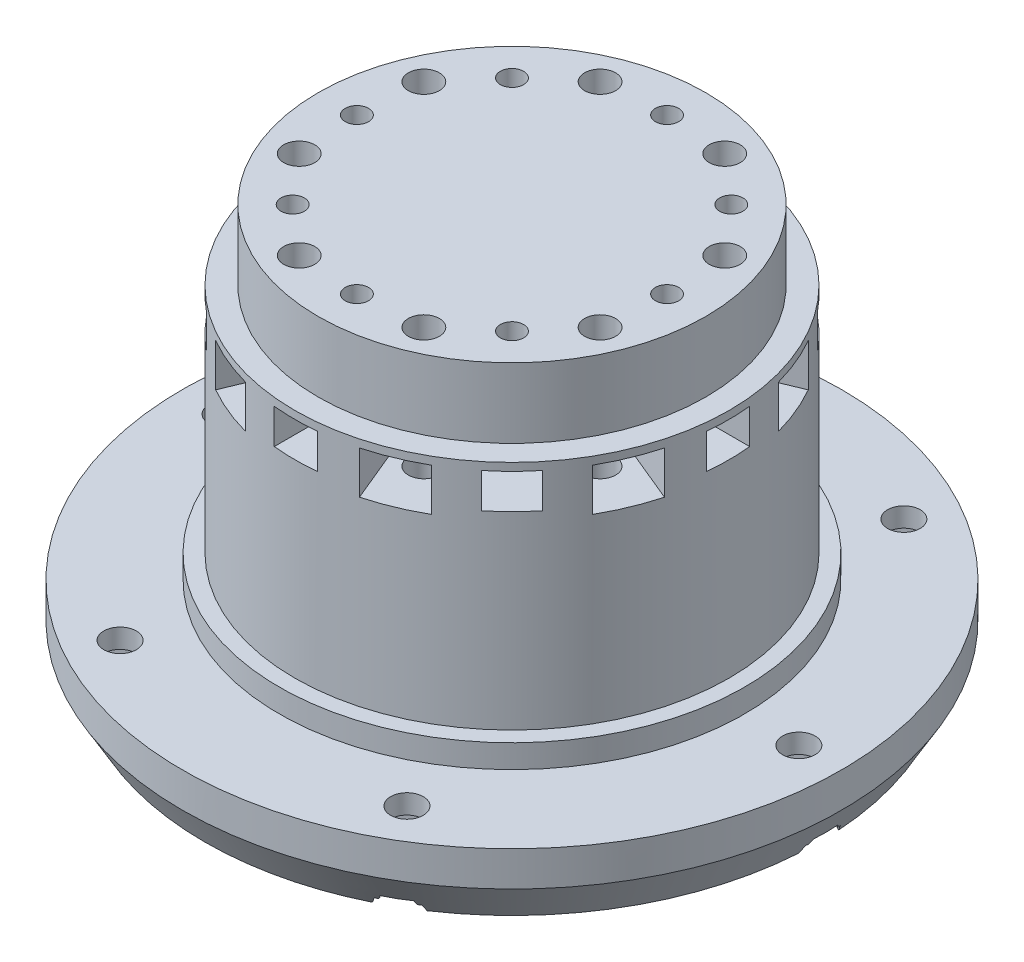
SolidWorks part; units mm, degrees
material "ABS"
ref_plane "Front Plane" through (0, 0, 0) normal (0, 0, 1) x (1, 0, 0)
ref_plane "Top Plane" through (0, 0, 0) normal (0, 1, 0) x (1, 0, 0)
ref_plane "Right Plane" through (0, 0, 0) normal (1, 0, 0) x (0, 0, -1)
sketch "Sketch1" plane through (0, 0, 0) normal (0, 0, 1) x (1, 0, 0)
  line L0 (0, 0) -> (0, 51.7742) construction
  line L1 (0, 0) -> (-42.5, 0)
  line L2 (-42.5, 0) -> (-42.5, 9.5)
  line L3 (-42.5, 9.5) -> (-30, 9.5)
  line L10 (0, 12.5) -> (0, 0)
  line L13 (-30, 9.5) -> (-30, 12.5)
  line L14 (-30, 12.5) -> (0, 12.5)
  dimension "D1" = 60
  dimension "D2" = 9.5
  dimension "D3" = 3
  dimension "D4" = 85
revolve "Revolve1" add sketch "Sketch1" angle 360 about L0
sketch "Sketch2" plane through (0, 0, 0) normal (0, 0, 1) x (1, 0, 0)
  line L0 (0, 0) -> (0, 30.5348) construction
  line L1 (-28, 41.4) -> (-28, 12.5)
  line L2 (0, -8.6) -> (-15, -8.6)
  line L3 (-15, -8.6) -> (-15, -0.6)
  line L4 (-15, -0.6) -> (-17.5, -0.6)
  line L5 (-17.5, -0.6) -> (-17.5, 0)
  line L6 (-42.5, 0) -> (42.5, 0) construction
  line L7 (-17.5, 0) -> (0, 0)
  line L8 (0, 0) -> (0, -8.6)
  line L9 (0, 51.4) -> (-25, 51.4)
  line L10 (-25, 51.4) -> (-25, 42.4)
  line L11 (-25, 42.4) -> (-28, 42.4)
  line L12 (-28, 42.4) -> (-28, 41.4)
  line L13 (30, 12.5) -> (-30, 12.5) construction
  line L14 (-28, 41.4) -> (0, 41.4) construction
  line L15 (0, 41.4) -> (0, 51.4)
  line L16 (-28, 12.5) -> (0, 12.5)
  line L17 (0, 12.5) -> (0, 41.4)
  dimension "D1" = 30
  dimension "D2" = 2.5
  dimension "D3" = 0.6
  dimension "D4" = 8
  dimension "D5" = 9
  dimension "D6" = 50
  dimension "D7" = 3
  dimension "D8" = 51
  dimension "D9" = 1
revolve "Revolve2" add sketch "Sketch2" angle 360 about L0
sketch "Sketch21" plane through (0, -8.6, 0) normal (0, -1, 0) x (1, 0, 0)
  circle A0 centre (0, 0) radius 3.175
  dimension "D1" = 6.35
extrude "Cut-Extrude13" cut sketch "Sketch21" against normal blind 3.16
sketch "Sketch24" [suppressed] plane through (0, -8.6, 0) normal (0, -1, 0) x (1, 0, 0)
  line L1 (-7.5, -0.75) -> (7.5, -0.75)
  line L2 (-7.5, -0.75) -> (-7.5, 0.75)
  line L3 (-7.5, 0.75) -> (7.5, 0.75)
  line L4 (7.5, -0.75) -> (7.5, 0.75)
  line L5 (-7.5, -0.75) -> (7.5, 0.75) construction
  line L6 (-7.5, 0.75) -> (7.5, -0.75) construction
  point P0 (0, 0)
  dimension "D1" = 15
  dimension "D2" = 1.5
extrude "Cut-Extrude17" [suppressed] cut sketch "Sketch24" against normal blind 5
sketch "Sketch18" plane through (0, 0, 0) normal (0, -1, 0) x (1, 0, 0)
  line L0 (-37, 0) -> (0, 0) construction
  circle A0 centre (-37, 0) radius 2.1
  circle A1 centre (-18.5, 32.0429) radius 2.1
  circle A2 centre (18.5, 32.0429) radius 2.1
  circle A3 centre (37, 0) radius 2.1
  circle A4 centre (18.5, -32.0429) radius 2.1
  circle A5 centre (-18.5, -32.0429) radius 2.1
  point P16 (0, 0)
  dimension "D2" = 4.2
  dimension "D1" = 37
  dimension "D3" = 6
extrude "Cut-Extrude11" cut sketch "Sketch18" against normal through all
sketch "Sketch19" plane through (0, 0, 0) normal (0, -1, 0) x (1, 0, 0)
  line L0 (-37, 0) -> (0, 0) construction
  line L1 (-33.5, -2.0207) -> (-33.5, 2.0207)
  line L2 (-33.5, 2.0207) -> (-37, 4.0415)
  line L3 (-37, 4.0415) -> (-40.5, 2.0207)
  line L4 (-40.5, 2.0207) -> (-40.5, -2.0207)
  line L5 (-40.5, -2.0207) -> (-37, -4.0415)
  line L6 (-37, -4.0415) -> (-33.5, -2.0207)
  circle A0 centre (-37, 0) radius 3.5 construction
  point P11 (-33.5, 0)
  dimension "D1" = 7
extrude "Cut-Extrude12" cut sketch "Sketch19" against normal blind 7
sketch "Sketch20" plane through (0, 0, 0) normal (0, -1, 0) x (1, 0, 0)
  line L0 (-40.5, 2.0207) -> (-37, 0) construction
  circle A0 centre (-40.5, 2.0207) radius 0.4
  circle A1 centre (-37, 4.0415) radius 0.4
  circle A2 centre (-33.5, 2.0207) radius 0.4
  circle A3 centre (-33.5, -2.0207) radius 0.4
  circle A4 centre (-37, -4.0415) radius 0.4
  circle A5 centre (-40.5, -2.0207) radius 0.4
  point P17 (-37, 0)
  dimension "D1" = 0.8
extrude "Boss-Extrude1" add sketch "Sketch20" against normal offset from surface (2.5 mm away) 4.5 up to face at (-37, 7, 0)
sketch "Sketch28" [suppressed] plane through (0, 7, 0) normal (0, -1, 0) x (1, 0, 0)
  circle A0 centre (-37, 0) radius 2.1 construction
  circle A1 centre (-37, 0) radius 2.1
extrude "Boss-Extrude3" [suppressed] add sketch "Sketch28" against normal blind 0.2
pattern_circular "CirPattern1" count 6 over 360 about axis through (0, 0, 0) along (0, -1, 0) of "Boss-Extrude1", "Cut-Extrude12", "Boss-Extrude3"
chamfer "Chamfer1" distance 5 angle 30 1 edges at (0, 0, -42.5) first distance on face at (0, 0, -42.5)
sketch "Sketch22" plane through (0, 51.4, 0) normal (0, 1, 0) x (1, 0, 0)
  line L0 (0, 0) -> (0, 20) construction
  line L1 (0, 0) -> (8.0364, 19.4015) construction
  circle A0 centre (0, 20) radius 1.5
  circle A1 centre (8.0364, 19.4015) radius 2
  circle A2 centre (14.1421, 14.1421) radius 1.5
  circle A3 centre (19.4015, 8.0364) radius 2
  circle A4 centre (20, 0) radius 1.5
  circle A5 centre (19.4015, -8.0364) radius 2
  circle A6 centre (14.1421, -14.1421) radius 1.5
  circle A7 centre (8.0364, -19.4015) radius 2
  circle A8 centre (0, -20) radius 1.5
  circle A9 centre (-8.0364, -19.4015) radius 2
  circle A10 centre (-14.1421, -14.1421) radius 1.5
  circle A11 centre (-19.4015, -8.0364) radius 2
  circle A12 centre (-20, 0) radius 1.5
  circle A13 centre (-19.4015, 8.0364) radius 2
  circle A14 centre (-14.1421, 14.1421) radius 1.5
  circle A15 centre (-8.0364, 19.4015) radius 2
  point P36 (0, 0)
  dimension "D1" = 3
  dimension "D2" = 4
  dimension "D3" = 22.5
  dimension "D4" = 20
  dimension "D5" = 21
  dimension "D6" = 8
extrude "Cut-Extrude14" cut sketch "Sketch22" against normal blind 20
sketch "Sketch23" plane through (0, 51.4, 0) normal (0, 1, 0) x (1, 0, 0)
  line L0 (-2.8, 21.6166) -> (-2.8, 27.8596)
  line L1 (2.8, 18.3834) -> (2.8, 21.6166)
  line L2 (2.8, 21.6166) -> (0, 23.2332) construction
  line L3 (0, 23.2332) -> (-2.8, 21.6166) construction
  line L4 (-2.8, 21.6166) -> (-2.8, 18.3834)
  line L5 (-2.8, 18.3834) -> (0, 16.7668)
  line L6 (0, 16.7668) -> (2.8, 18.3834)
  line L7 (10.5318, 16.1494) -> (12.1005, 19.9365)
  line L8 (12.1005, 19.9365) -> (9.605, 23.1886) construction
  line L9 (9.605, 23.1886) -> (5.5409, 22.6536) construction
  line L10 (5.5409, 22.6536) -> (3.9722, 18.8664)
  line L11 (3.9722, 18.8664) -> (6.4677, 15.6143)
  line L12 (6.4677, 15.6143) -> (10.5318, 16.1494)
  line L13 (2.8, 21.6166) -> (2.8, 27.8596)
  line L14 (5.5409, 22.6536) -> (7.3489, 27.0184)
  line L15 (12.1005, 19.9365) -> (13.9084, 24.3013)
  line L16 (0, 0) -> (0, 20) construction
  line L17 (8.0364, 19.4015) -> (0, 0) construction
  circle A0 centre (0, 20) radius 2.8 construction
  circle A1 centre (8.0364, 19.4015) radius 3.55 construction
  circle A2 centre (0, 0) radius 28 construction
  circle A3 centre (0, 0) radius 28 construction
  arc A4 (2.8, 27.8596) -> (-2.8, 27.8596) centre (0, 0) ccw
  arc A5 (13.9084, 24.3013) -> (7.3489, 27.0184) centre (0, 0) ccw
  circle M35 centre (8.0364, 19.4015) radius 2
  circle M36 centre (0, 20) radius 1.5
  circle M37 centre (0, 0) radius 25
  dimension "D1" = 5.6
  dimension "D2" = 7.1
extrude "Cut-Extrude15" cut sketch "Sketch23" against normal blind 4.5 from offset 10 contours L1 L13 L0 L4 L5 L6 M37 M36 | L13 A4 L0 M37 region at (0, 51.4, -21.5043) region at (0, 51.4, -26.4504) offset against normal yes
extrude "Cut-Extrude16" cut sketch "Sketch23<3>" against normal blind 5.5 from offset 10 contours L7 L15 L14 L10 L11 L12 M37 M35 | L15 A5 L14 M37 region at (9.52, 51.4, -22.9834) region at (10.1105, 51.4, -24.409) offset against normal yes
sketch "Sketch23<3>" plane through (0, 51.4, 0) normal (0, 1, 0) x (1, 0, 0) same geometry as "Sketch23"
pattern_circular "CirPattern2" count 8 over 360 about axis through (0, 0, 0) along (0, -1, 0) of "Cut-Extrude16", "Cut-Extrude15" reverse direction yes
sketch "Sketch25" [suppressed] plane through (0, 42.4, 0) normal (0, -1, 0) x (1, 0, 0)
  circle A0 centre (0, 0) radius 28 construction
  circle A1 centre (0, 0) radius 28
extrude "Boss-Extrude2" [suppressed] add sketch "Sketch25" against normal blind 0.2
sketch "Sketch26" [suppressed] plane through (0, 0, 0) normal (0, 0, 1) x (1, 0, 0)
  line L0 (0, 0) -> (0, 51.4) construction
  line L1 (25, 51.4) -> (-25, 51.4) construction
  line L2 (-8.55, 49) -> (-8.55, 42)
  line L3 (-10.55, 41.5) -> (-12, 41.5)
  line L4 (-12, 41.5) -> (-13.2124, 39.4)
  line L5 (-13.2124, 39.4) -> (-28, 39.4)
  line L6 (-28, 42.4) -> (-28, 12.5) construction
  line L7 (-28, 39.4) -> (-28, 51.4)
  line L8 (-28, 51.4) -> (-8.55, 51.4)
  line L9 (-8.55, 42) -> (-10.55, 42)
  line L10 (-10.55, 42) -> (-10.55, 41.5)
  line L11 (-8.55, 51.4) -> (-8.55, 49) construction
  line L12 (0, 51.4) -> (-8.55, 51.4)
  line L13 (0, 51.4) -> (0, 49)
  line L14 (0, 49) -> (-8.55, 49)
  line L15 (-8.55, 51.4) -> (-8.55, 49) construction
  dimension "D1" = 17.1
  dimension "D2" = 2
  dimension "D3" = 0.5
  dimension "D4" = 24
  dimension "D5" = 12
  dimension "D6" = 60
  dimension "D7" = 7
  dimension "D8" = 2.4
revolve "Cut-Revolve1" [suppressed] cut sketch "Sketch26" angle 360 about L0
chamfer "Chamfer2" [suppressed] distance 7 angle 70
sketch "Sketch31" [suppressed] plane through (0, 49, 0) normal (0, 1, 0) x (1, 0, 0)
  line L0 (5, 0) -> (-5, 0) construction
  circle A0 centre (-5, 0) radius 2
  circle A1 centre (5, 0) radius 2
  point P8 (0, 0)
  dimension "D1" = 4
  dimension "D2" = 10
extrude "Cut-Extrude18" [suppressed] cut sketch "Sketch31" against normal up to surface (52.6 mm away) up to face at (0, 0, 0)
equation "\"pinwheel_roller_radius\"= 3.5"
equation "\"pinwheel_roller_position\"= 34"
equation "\"pinwheel_tooth_count\"= 14"
equation "\"cycloid_eccentricity\"= 1.5"
equation "\"cycloid_clearance\"= 0.05"
equation "\"output_roller_position\"= 20"
equation "\"output_roller_radius\"= 9"
equation "\"output_stiffener_position\"= 21"
equation "\"output_stiffener_radius\"= 6"
equation "\"disk_thickness\"= 25"
equation "\"preload_angle\"= 1.5"
equation "\"preload_height\"= 3"
equation "\"preload_screw_count\"=4"
